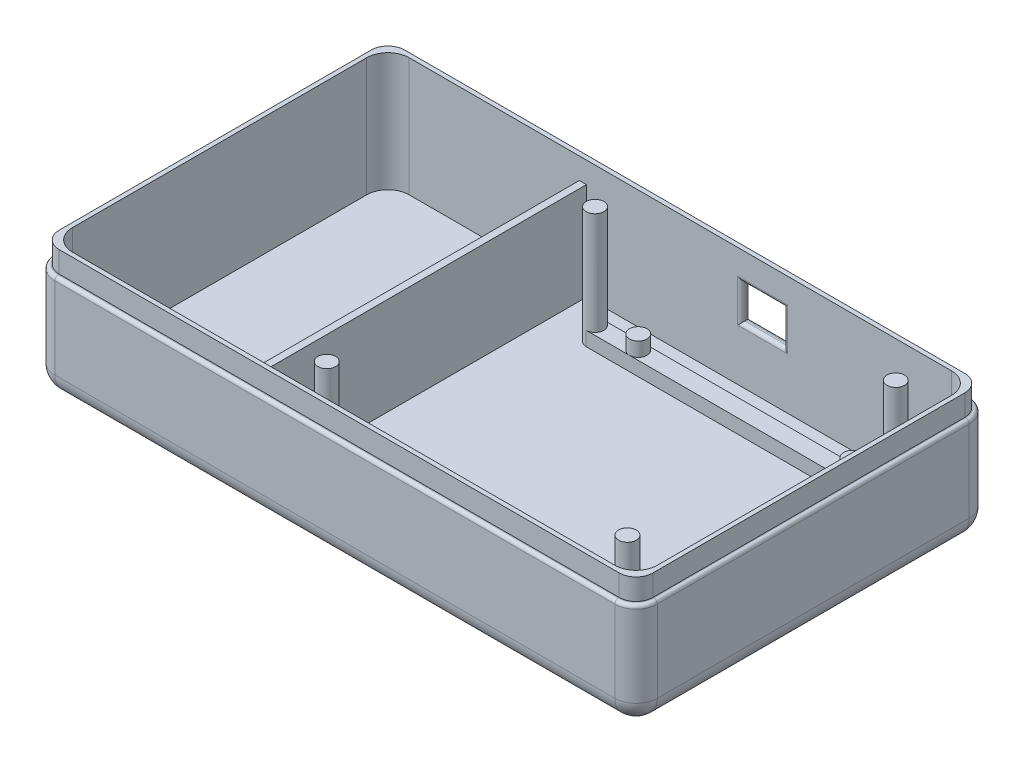
SolidWorks part; units mm, degrees
ref_plane "Front Plane" through (0, 0, 0) normal (0, 0, 1) x (1, 0, 0)
ref_plane "Top Plane" through (0, 0, 0) normal (0, 1, 0) x (1, 0, 0)
ref_plane "Right Plane" through (0, 0, 0) normal (1, 0, 0) x (0, 0, -1)
sketch "Sketch2" plane through (0, 0, 0) normal (0, 1, 0) x (1, 0, 0)
  line L0 (-41.25, 23.75) -> (41.25, 23.75)
  line L1 (-42.5, -25) -> (42.5, -25)
  line L2 (-42.5, -25) -> (-42.5, 25)
  line L3 (-42.5, 25) -> (42.5, 25)
  line L4 (42.5, -25) -> (42.5, 25)
  line L5 (-42.5, -25) -> (42.5, 25) construction
  line L6 (-42.5, 25) -> (42.5, -25) construction
  line L7 (41.25, -23.75) -> (41.25, 23.75)
  line L8 (-41.25, -23.75) -> (41.25, -23.75)
  line L9 (-41.25, -23.75) -> (-41.25, 23.75)
  line L10 (-14.25, -23.75) -> (-14.25, 23.75)
  line L11 (-13.25, -23.75) -> (-13.25, 23.75)
  point P0 (0, 0)
  dimension "D1" = 1.25
  dimension "85" = 85
  dimension "50" = 50
  dimension "D4" = 1.25
  dimension "D2" = 27
  dimension "D3" = 1
extrude "Boss-Extrude3" add sketch "Sketch2" along normal blind 1.25 contours L11 L8 L7 L0 | L8 L11 L0 L10 | L8 L10 L0 L9 region at (-27.75, 0, 0) region at (-13.75, 0, 0) region at (14, 0, 0)
extrude "Boss-Extrude4" add sketch "Sketch2<4>" along normal blind 18 contours L1 L4 L3 L2 L8 L9 L0 L7 region at (-41.5138, 0, 0)
sketch "Sketch2<4>" plane through (0, 0, 0) normal (0, 1, 0) x (1, 0, 0) same geometry as "Sketch2"
extrude "Boss-Extrude5" add sketch "Sketch2<5>" along normal blind 15 contours L8 L11 L0 L10 region at (-13.75, 0, 0)
sketch "Sketch2<5>" plane through (0, 0, 0) normal (0, 1, 0) x (1, 0, 0) same geometry as "Sketch2"
sketch3d "3DSketch2"
  line L0 (40.543, 1.25, 23.75) -> (40.543, 1.25, -23.75)
  line L1 (40.543, 1.25, 23.75) -> (40.543, 1.25, -23.75)
  line L2 (-13.25, 1.25, -23.75) -> (-13.25, 1.25, 23.75) construction
  line L3 (-12.543, 1.25, 21.844) -> (-12.543, 1.25, -21.844)
  line L4 (-12.543, 1.25, 21.844) -> (40.543, 1.25, 21.844)
  line L5 (40.543, 1.25, 21.844) -> (40.543, 1.25, -21.844)
  line L6 (-12.543, 1.25, -21.844) -> (40.543, 1.25, -21.844)
  line L7 (-12.543, 1.25, 21.844) -> (40.543, 1.25, -21.844) construction
  line L8 (40.543, 1.25, 21.844) -> (-12.543, 1.25, -21.844) construction
  line L9 (-12.543, 1.25, -23.75) -> (-12.543, 1.25, 23.75)
  line L10 (-12.543, 1.25, -23.75) -> (-12.543, 1.25, 23.75)
  line L11 (-7.209, 1.25, -23.75) -> (-7.209, 1.25, 23.75)
  line L12 (-7.209, 1.25, -23.75) -> (-7.209, 1.25, 23.75)
  line L13 (-1.113, 1.25, -23.75) -> (-1.113, 1.25, 23.75)
  line L14 (-1.113, 1.25, -23.75) -> (-1.113, 1.25, 23.75)
  line L15 (41.25, 1.25, 23.75) -> (41.25, 1.25, -23.75) construction
  line L16 (-13.25, 1.25, -23.75) -> (41.25, 1.25, -23.75) construction
  line L17 (-13.25, 1.25, -18.923) -> (41.25, 1.25, -18.923)
  line L18 (-13.25, 1.25, -18.923) -> (41.25, 1.25, -18.923)
  line L19 (35.209, 1.25, 23.75) -> (35.209, 1.25, -23.75)
  line L20 (35.209, 1.25, 23.75) -> (35.209, 1.25, -23.75)
  line L21 (29.113, 1.25, 23.75) -> (29.113, 1.25, -23.75)
  line L22 (29.113, 1.25, 23.75) -> (29.113, 1.25, -23.75)
  line L23 (-13.25, 1.25, 18.923) -> (41.25, 1.25, 18.923)
  line L24 (-13.25, 1.25, 18.923) -> (41.25, 1.25, 18.923)
  point P8 (14, 1.25, 0)
  dimension "D1" = 43.688
  dimension "D2" = 53.086
  dimension "D4" = 0.707
  dimension "D3" = 0.707
  dimension "D7" = 0.707
  dimension "D8" = 1.906
  dimension "D5" = 6.041
  dimension "D6" = 12.137
  dimension "D9" = 4.827
  dimension "D10" = 0.707
  dimension "D11" = 6.041
  dimension "D12" = 12.137
  dimension "D13" = 4.827
sketch "Sketch5" plane through (0, 1.25, 0) normal (0, 1, 0) x (1, 0, 0)
  line L0 (-7.209, 23.75) -> (-7.209, -23.75) construction
  line L1 (-13.25, 18.923) -> (41.25, 18.923) construction
  line L2 (35.209, -23.75) -> (35.209, 23.75) construction
  line L3 (-13.25, -18.923) -> (41.25, -18.923) construction
  circle A0 centre (-7.209, 18.923) radius 1.2446
  circle A1 centre (35.209, 18.923) radius 1.2446
  circle A2 centre (-7.209, -18.923) radius 1.2446
  circle A3 centre (35.209, -18.923) radius 1.2446
  dimension "D1" = 2.4892
extrude "Boss-Extrude6" add sketch "Sketch5" along normal blind 16.5
sketch3d "3DSketch4" plane through (0, 0, 0) normal (0, 0, 1) x (1, 0, 0)
sketch "Sketch6" plane through (0, 1.25, 0) normal (0, 1, 0) x (1, 0, 0)
  line L0 (-1.113, 23.75) -> (-1.113, -23.75) construction
  line L1 (-13.25, 18.923) -> (41.25, 18.923) construction
  line L2 (29.113, -23.75) -> (29.113, 23.75) construction
  line L3 (-13.25, -18.923) -> (41.25, -18.923) construction
  circle A0 centre (-1.113, 18.923) radius 1.2446
  circle A1 centre (29.113, 18.923) radius 1.2446
  circle A2 centre (-1.113, -18.923) radius 1.2446
  circle A3 centre (29.113, -18.923) radius 1.2446
  dimension "D1" = 2.4892
extrude "Boss-Extrude7" add sketch "Sketch6" along normal blind 4
sketch "Sketch7" plane through (0, 1.25, 0) normal (0, 1, 0) x (1, 0, 0)
  line L0 (-7.209, 23.75) -> (-7.209, -23.75) construction
  line L1 (-7.209, -20.1676) -> (35.209, -20.1676)
  line L2 (-7.209, -20.1676) -> (-7.209, -17.6784)
  line L3 (-7.209, -17.6784) -> (35.209, -17.6784)
  line L4 (35.209, -20.1676) -> (35.209, -17.6784)
  line L5 (35.209, -23.75) -> (35.209, 23.75) construction
  line L7 (-7.209, 20.1676) -> (35.209, 20.1676)
  line L8 (-7.209, 20.1676) -> (-7.209, 17.6784)
  line L9 (-7.209, 17.6784) -> (35.209, 17.6784)
  line L10 (35.209, 20.1676) -> (35.209, 17.6784)
  circle A0 centre (-7.209, -18.923) radius 1.2446 construction
  circle A1 centre (35.209, -18.923) radius 1.2446 construction
  circle A2 centre (-7.209, 18.923) radius 1.2446 construction
  circle A3 centre (35.209, 18.923) radius 1.2446 construction
extrude "Boss-Extrude9" add sketch "Sketch7" along normal blind 2
fillet "Fillet2" radius 3 12 edges at (42.5, 0, 0) (0, 0, -25) (-42.5, 0, 0) (0, 0, 25) (-42.5, 9, 25) (-41.25, 9.625, 23.75) (-41.25, 9.625, -23.75) (-42.5, 9, -25) (41.25, 9.625, 23.75) (42.5, 9, 25) (42.5, 9, -25) (41.25, 9.625, -23.75)
sketch "Sketch10" plane through (0, 18, 0) normal (0, 1, 0) x (1, 0, 0)
  line L8 (-41.875, 22) -> (-41.875, -22)
  line L9 (-39.5, -24.375) -> (39.5, -24.375)
  line L10 (41.875, -22) -> (41.875, 22)
  line L11 (39.5, 24.375) -> (-39.5, 24.375)
  line L12 (-41.875, 22) -> (-41.875, -22)
  line L13 (-39.5, -24.375) -> (39.5, -24.375)
  line L14 (41.875, -22) -> (41.875, 22)
  line L15 (39.5, 24.375) -> (-39.5, 24.375)
  arc A8 (-41.875, -22) -> (-39.5, -24.375) centre (-39.5, -22) ccw
  arc A9 (39.5, -24.375) -> (41.875, -22) centre (39.5, -22) ccw
  arc A10 (41.875, 22) -> (39.5, 24.375) centre (39.5, 22) ccw
  arc A11 (-39.5, 24.375) -> (-41.875, 22) centre (-39.5, 22) ccw
  arc A12 (-41.875, -22) -> (-39.5, -24.375) centre (-39.5, -22) ccw
  arc A13 (39.5, -24.375) -> (41.875, -22) centre (39.5, -22) ccw
  arc A14 (41.875, 22) -> (39.5, 24.375) centre (39.5, 22) ccw
  arc A15 (-39.5, 24.375) -> (-41.875, 22) centre (-39.5, 22) ccw
  dimension "D1" = 0.625
extrude "Cut-Extrude4" cut sketch "Sketch10" along direction (0, 1, 0) on the side against the normal offset from surface (3 mm away) 3 flip side to cut up to face at (0, 18, 0)
fillet "Fillet3" radius 0.5 8 edges at (-41.6213, 15, 24.1213) (-42.5, 15, 0) (-41.6213, 15, -24.1213) (0, 15, -25) (41.6213, 15, -24.1213) (42.5, 15, 0) (41.6213, 15, 24.1213) (0, 15, 25)
ref_plane "Plane2" through (0, 0, -25) normal (0, 0, 1) x (1, 0, 0)
sketch "Sketch14" plane through (0, 0, -25) normal (0, 0, 1) x (1, 0, 0)
  line L0 (42.5, 0) -> (-42.5, 0)
  line L1 (-15.5, 18) -> (-15.5, 0) construction
  line L2 (42.5, 0) -> (-42.5, 0)
  line L3 (42.5, 0) -> (42.5, 18)
  line L4 (42.5, 18) -> (-42.5, 18)
  line L5 (-42.5, 0) -> (-42.5, 18)
  line L6 (-14.5, 18) -> (-14.5, 0) construction
  line L7 (42.5, 0) -> (-14.5, 18) construction
  line L8 (-14.5, 18) -> (42.5, 18) construction
  line L9 (42.5, 18) -> (-14.5, 0) construction
  line L10 (31.4778, 2) -> (31.4778, 0) construction
  line L11 (40.543, 16) -> (-12.543, 16)
  line L12 (40.543, 16) -> (40.543, 2)
  line L13 (40.543, 2) -> (-12.543, 2)
  line L14 (-12.543, 16) -> (-12.543, 2)
  line L15 (40.543, 16) -> (-12.543, 2) construction
  line L16 (40.543, 2) -> (-12.543, 16) construction
  line L17 (3.967, 16) -> (3.967, 2) construction
  line L18 (11.587, 16) -> (11.587, 2) construction
  line L19 (19.207, 16) -> (19.207, 2) construction
  line L20 (40.543, 9) -> (-12.543, 9) construction
  line L21 (40.543, 14) -> (-12.543, 14) construction
  line L22 (19.207, 9) -> (3.967, 14) construction
  line L23 (19.207, 14) -> (3.967, 9) construction
  line L25 (14.587, 9) -> (8.587, 9)
  line L26 (14.587, 9) -> (14.587, 14)
  line L27 (14.587, 14) -> (8.587, 14)
  line L28 (8.587, 9) -> (8.587, 14)
  line L29 (14.587, 9) -> (8.587, 14) construction
  line L30 (14.587, 14) -> (8.587, 9) construction
  point P10 (14, 9)
  point P31 (11.587, 11.5)
  dimension "D1" = 18
  dimension "D2" = 27
  dimension "D3" = 1
  dimension "D4" = 53.086
  dimension "D5" = 2
  dimension "D6" = 16.51
  dimension "D7" = 24.13
  dimension "D8" = 31.75
  dimension "D9" = 7
  dimension "D10" = 12
  dimension "D11" = 5
  dimension "D12" = 6
extrude "Cut-Extrude5" cut sketch "Sketch14" along normal blind 2 contours L28 L25 L26 L27 region at (11.587, 11.5, -25)
fillet "Fillet4" radius 0.5 8 edges at (11.587, 9, -23.75) (8.587, 11.5, -23.75) (11.587, 14, -23.75) (14.587, 11.5, -23.75) (11.587, 9, -25) (8.587, 11.5, -25) (11.587, 14, -25) (14.587, 11.5, -25)
